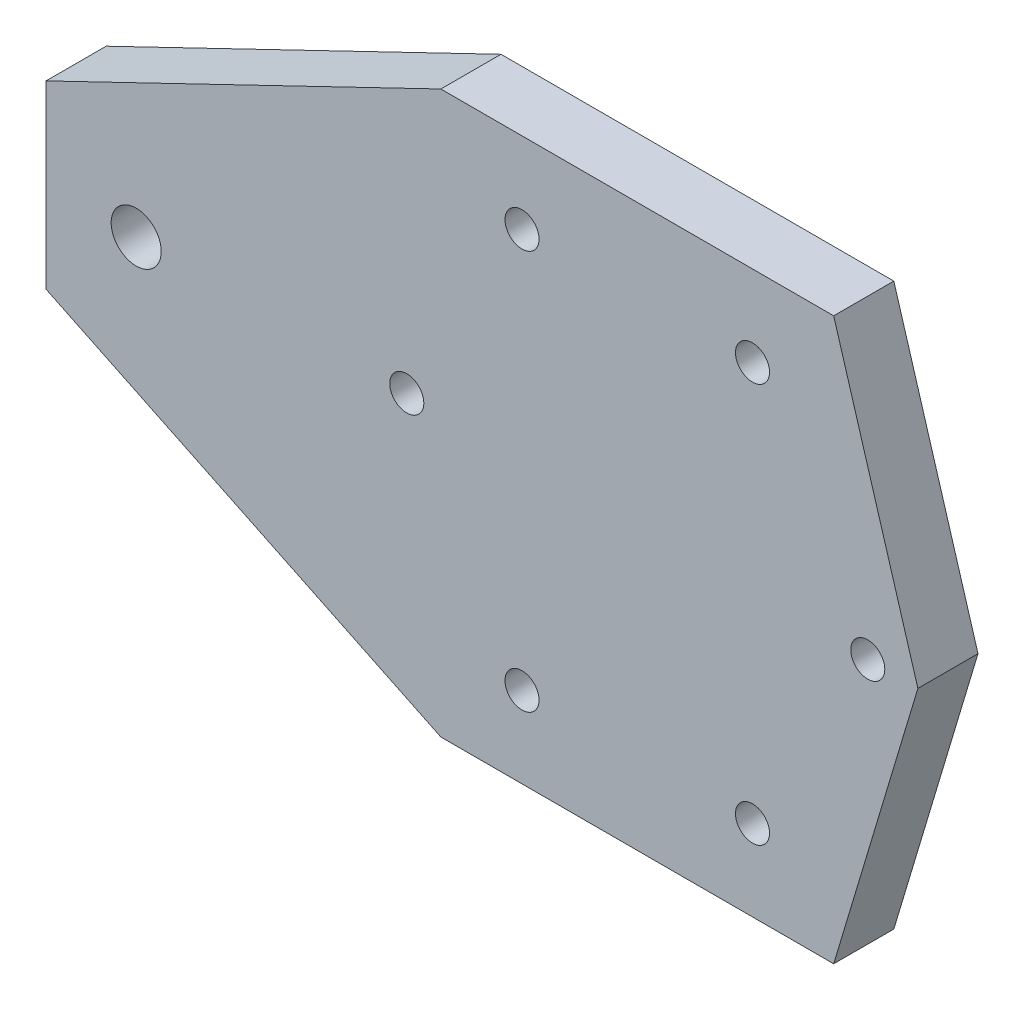
SolidWorks part; units mm, degrees
ref_plane "Front Plane" through (0, 0, 0) normal (0, 0, 1) x (1, 0, 0)
ref_plane "Top Plane" through (0, 0, 0) normal (0, 1, 0) x (1, 0, 0)
ref_plane "Right Plane" through (0, 0, 0) normal (1, 0, 0) x (0, 0, -1)
sketch "SK_Crank_Plate" plane through (0, 0, 0) normal (0, 0, 1) x (1, 0, 0)
  line L0 (-59, -9) -> (-19.6, -28)
  line L1 (-19.6, -28) -> (19.6, -28)
  line L2 (19.6, -28) -> (28, 0)
  line L3 (28, 0) -> (19.6, 28)
  line L4 (19.6, 28) -> (-19.6, 28)
  line L5 (-19.6, 28) -> (-59, 9)
  line L6 (-59, 9) -> (-59, -9)
  circle A0 centre (23, 0) radius 1.7
  circle A1 centre (11.5, 19.9186) radius 1.7
  circle A2 centre (-11.5, 19.9186) radius 1.7
  circle A3 centre (-23, 0) radius 1.7
  circle A4 centre (-11.5, -19.9186) radius 1.7
  circle A5 centre (11.5, -19.9186) radius 1.7
  circle A6 centre (-50, 0) radius 2.5
  dimension "D14_SK_Crank_Plate" = 3.4
  dimension "D16_SK_Crank_Plate" = 3.4
  dimension "D19_SK_Crank_Plate" = 3.4
  dimension "D22_SK_Crank_Plate" = 3.4
  dimension "D24_SK_Crank_Plate" = 3.4
  dimension "D27_SK_Crank_Plate" = 3.4
  dimension "D30_SK_Crank_Plate" = 5
  dimension "P1" = 59
  dimension "P2" = 9
  dimension "P3" = 19.6
  dimension "P4" = 28
  dimension "P5" = 19.6
  dimension "P6" = 28
  dimension "P7" = 28
  dimension "P8" = 19.6
  dimension "P9" = 28
  dimension "P10" = 19.6
  dimension "P11" = 28
  dimension "P12" = 59
  dimension "P13" = 9
  dimension "P15" = 23
  dimension "P17" = 11.5
  dimension "P18" = 19.9186
  dimension "P20" = 11.5
  dimension "P21" = 19.9186
  dimension "P23" = 23
  dimension "P25" = 11.5
  dimension "P26" = 19.9186
  dimension "P28" = 11.5
  dimension "P29" = 19.9186
  dimension "P31" = 50
extrude "Crank_Plate" add sketch "SK_Crank_Plate" along normal blind 6
equation "\"Crank_radius\" = 50"
